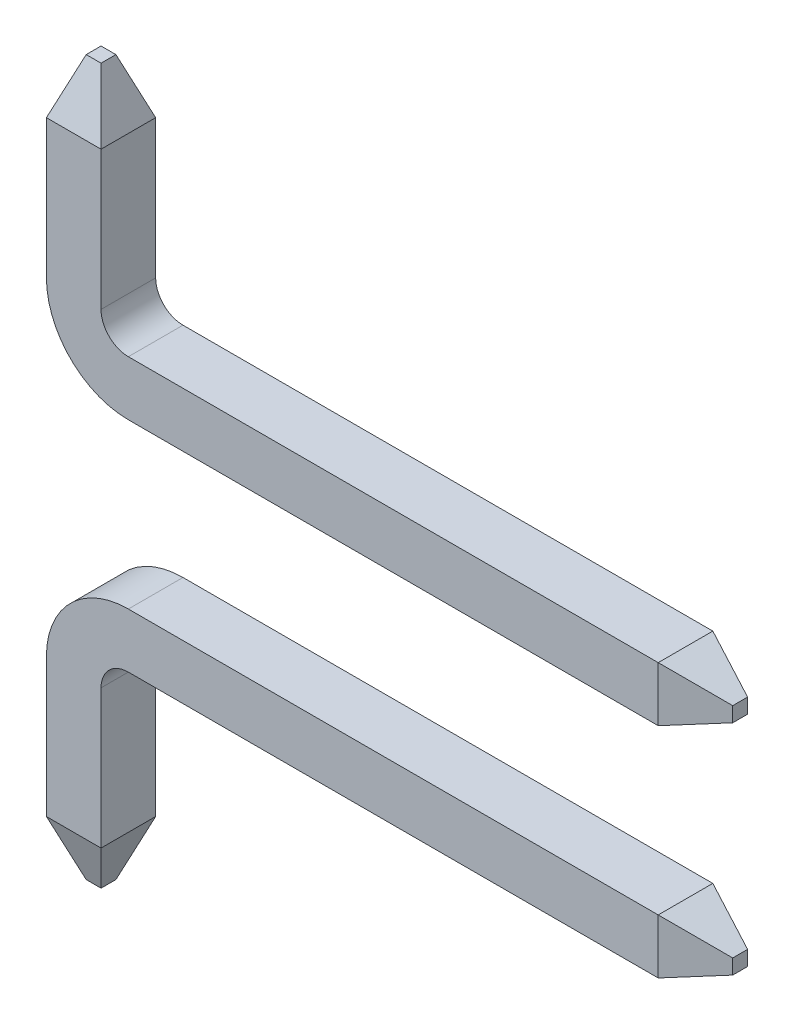
SolidWorks part; units mm, degrees
ref_plane "Front Plane" through (0, 0, 0) normal (0, 0, 1) x (1, 0, 0)
ref_plane "Top Plane" through (0, 0, 0) normal (0, 1, 0) x (1, 0, 0)
ref_plane "Right Plane" through (0, 0, 0) normal (1, 0, 0) x (0, 0, -1)
sketch "Sketch1" plane through (0, 0, 0) normal (0, 1, 0) x (1, 0, 0)
  line L1 (0, 0) -> (0.5, 0)
  line L2 (0, 0) -> (0, 0.5)
  line L3 (0, 0.5) -> (0.5, 0.5)
  line L4 (0.5, 0) -> (0.5, 0.5)
sketch "Sketch2" plane through (0, 0, 0) normal (0, 0, 1) x (1, 0, 0)
  line L0 (0, 0) -> (0.5, 0) construction
  line L1 (0.25, 0) -> (0.25, 1.77) construction
  line L2 (0.25, 1.77) -> (5.6, 1.77) construction
  line L3 (0.25, 0) -> (0.25, 1.27)
  line L4 (0.75, 1.77) -> (5.6, 1.77)
  line L5 (0.25, 0) -> (0.75, 0) construction
  line L6 (0.75, 0) -> (0.75, 1.77) construction
  line L7 (0.75, 1.27) -> (0.25, 1.27) construction
  arc A0 (0.25, 1.27) -> (0.75, 1.77) centre (0.75, 1.27) cw
sweep "Sweep4" add profiles "Sketch1" path "Sketch2"
sketch "Sketch6" plane through (5.6, 0, 0) normal (1, 0, 0) x (0, 0, -1)
  line L1 (0, 2.02) -> (0.5, 2.02)
  line L2 (0, 2.02) -> (0, 1.52)
  line L3 (0, 1.52) -> (0.5, 1.52)
  line L4 (0.5, 2.02) -> (0.5, 1.52)
extrude "Boss-Extrude1" add sketch "Sketch6" along normal blind 0.5 draft 20
sketch "Sketch7" plane through (0, 0, 0) normal (0, -1, 0) x (1, 0, 0)
  line L1 (0, 0) -> (0.5, 0)
  line L2 (0, 0) -> (0, -0.5)
  line L3 (0, -0.5) -> (0.5, -0.5)
  line L4 (0.5, 0) -> (0.5, -0.5)
extrude "Boss-Extrude2" add sketch "Sketch7" along normal blind 0.5 draft 20
ref_plane "Plane1" through (0, 2.77, 0) normal (0, 1, 0) x (-1, 0, 0)
mirror "Mirror3" about plane through (0, 2.77, 0) normal (0, 1, 0) of bodies 104
